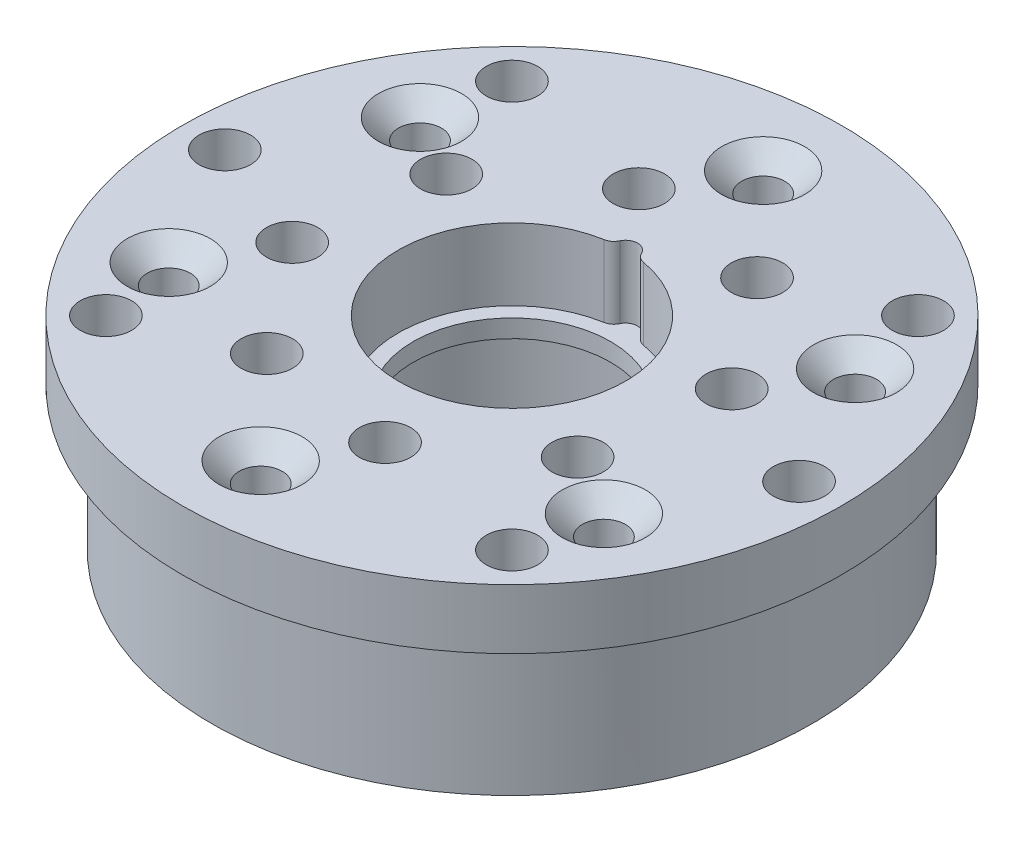
SolidWorks part; units mm, degrees
ref_plane "Front Plane" through (0, 0, 0) normal (0, 0, 1) x (1, 0, 0)
ref_plane "Top Plane" through (0, 0, 0) normal (0, 1, 0) x (1, 0, 0)
ref_plane "Right Plane" through (0, 0, 0) normal (1, 0, 0) x (0, 0, -1)
sketch "Sketch1" plane through (0, 0, 0) normal (0, 1, 0) x (1, 0, 0)
  circle A0 centre (0, 0) radius 21 construction
  circle A1 centre (0, 21) radius 2.5
  circle A2 centre (18.1865, 10.5) radius 2.5
  circle A3 centre (18.1865, -10.5) radius 2.5
  circle A4 centre (0, -21) radius 2.5
  circle A5 centre (-18.1865, -10.5) radius 2.5
  circle A6 centre (-18.1865, 10.5) radius 2.5
  circle A7 centre (0, 0) radius 25.1
  circle A8 centre (0, 0) radius 8.25
  point P18 (0, 0)
  dimension "D1" = 42
  dimension "D2" = 5
  dimension "D4" = 50.2
  dimension "D5" = 16.5
  dimension "D3" = 6
extrude "Boss-Extrude1" add sketch "Sketch1" along normal blind 10
sketch "Sketch2" plane through (0, 10, 0) normal (0, 1, 0) x (1, 0, 0)
  circle A0 centre (0, 0) radius 9.5
  circle A1 centre (0, 0) radius 15.5
  dimension "D1" = 19
  dimension "D2" = 6
extrude "Boss-Extrude2" add sketch "Sketch2" along normal blind 8.5
sketch "Sketch4" plane through (0, 10, 0) normal (0, 1, 0) x (1, 0, 0)
  circle A0 centre (0, 0) radius 9.5 construction
  circle A1 centre (0, 0) radius 8.25 construction
  circle A2 centre (0, 0) radius 9.5
  circle A3 centre (0, 0) radius 8.25
extrude "Boss-Extrude3" add sketch "Sketch4" along normal blind 2.5
sketch "Sketch3" plane through (0, 0, 0) normal (0, -1, 0) x (1, 0, 0)
  circle A0 centre (0, 0) radius 12.5
  dimension "D1" = 25
extrude "Cut-Extrude1" cut sketch "Sketch3" against normal blind 11
chamfer "Chamfer1" distance 3 angle 45 1 edges at (0, 11, -12.5)
sketch "Sketch5" plane through (0, 10, 0) normal (0, 1, 0) x (1, 0, 0)
  circle A0 centre (0, 21) radius 2.5
  circle A1 centre (18.1872, 10.4996) radius 2.5
  circle A2 centre (18.1872, -10.5011) radius 2.5
  circle A3 centre (0, -21.0014) radius 2.5
  circle A4 centre (-18.1872, -10.5011) radius 2.5
  circle A5 centre (-18.1872, 10.4996) radius 2.5
  circle A6 centre (0, 0) radius 25.1 construction
  circle A7 centre (0, 0) radius 25.1
  circle A8 centre (0, 0) radius 15.5 construction
  circle A9 centre (0, 0) radius 15.5
  circle A10 centre (0, 21) radius 2.5 construction
  point P15 (0, -0.0007)
  dimension "D2" = 6
extrude "Boss-Extrude4" add sketch "Sketch5" along normal blind 8.5
sketch "Sketch6" plane through (0, 18.5, 0) normal (0, 1, 0) x (1, 0, 0)
  circle A0 centre (0, 0) radius 25.1 construction
  circle A1 centre (0, 0) radius 25.1
  circle A2 centre (0, 0) radius 27.55
  dimension "D1" = 55.1
extrude "Boss-Extrude5" add sketch "Sketch6" against normal blind 5
sketch "Sketch8" plane through (0, 18.5, 0) normal (0, 1, 0) x (1, 0, 0)
  circle A0 centre (0, 9.5) radius 1
  circle A1 centre (0, 0) radius 9.5 construction
  circle A2 centre (0, 0) radius 9.5 construction
  dimension "D1" = 2
extrude "Cut-Extrude2" cut sketch "Sketch8" against normal up to surface (6 mm away) up to face at (0, 12.5, 9.5)
fillet "Fillet1" radius 1 2 edges at (0.9986, 15.5, -9.4474) (-0.9986, 15.5, -9.4474)
sketch "Sketch11" plane through (0, 18.5, 0) normal (0, 1, 0) x (1, 0, 0)
  line L0 (0, 0) -> (17.55, 30.3975) construction
  circle A0 centre (0, 0) radius 15 construction
  circle A1 centre (7.5, 12.9904) radius 2.15
  circle A2 centre (14.4889, 3.8823) radius 2.15
  circle A3 centre (12.9904, -7.5) radius 2.15
  circle A4 centre (3.8823, -14.4889) radius 2.15
  circle A5 centre (-7.5, -12.9904) radius 2.15
  circle A6 centre (-14.4889, -3.8823) radius 2.15
  circle A7 centre (0, 0) radius 24 construction
  circle A8 centre (-24, 0) radius 2.15
  circle A9 centre (-16.9706, 16.9706) radius 2.15
  circle A11 centre (16.9706, 16.9706) radius 2.15
  circle A12 centre (24, 0) radius 2.15
  circle A13 centre (16.9706, -16.9706) radius 2.15
  circle A14 centre (-12.9904, 7.5) radius 2.15
  circle A15 centre (-3.8823, 14.4889) radius 2.15
  circle A17 centre (-16.9706, -16.9706) radius 2.15
  circle A18 centre (0, -24) radius 2.15 [skipped]
  circle A19 centre (0, 24) radius 2.15 [skipped]
  point P18 (0, 0)
  point P32 (0, 0)
  point P35 (0, 0)
  point P40 (0, 0)
  point P41 (-5.5561, 21.5179)
  point P42 (0, 0)
  point P43 (0, 24)
  point P44 (0, 24)
  point P45 (0, 0)
  dimension "D2" = 30
  dimension "D3" = 4.3
  dimension "D5" = 48
  dimension "D6" = 8
  dimension "D1" = 60
  dimension "D4" = 8
extrude "Cut-Extrude3" cut sketch "Sketch11" against normal blind 4.8
sketch "Sketch12" plane through (0, 0, 0) normal (0, -1, 0) x (1, 0, 0)
  circle A0 centre (0, 0) radius 25.1 construction
  circle A1 centre (18.1865, 10.5) radius 2.5 construction
  circle A2 centre (18.1865, -10.5) radius 2.5 construction
  circle A3 centre (0, -21) radius 2.5 construction
  circle A4 centre (-18.1865, -10.5) radius 2.5 construction
  circle A5 centre (-18.1865, 10.5) radius 2.5 construction
  circle A6 centre (0, 21) radius 2.5 construction
  circle A7 centre (0, 0) radius 12.5 construction
  circle A8 centre (0, 0) radius 25.1
  circle A9 centre (18.1865, 10.5) radius 2.5
  circle A10 centre (18.1865, -10.5) radius 2.5
  circle A11 centre (0, -21) radius 2.5
  circle A12 centre (-18.1865, -10.5) radius 2.5
  circle A13 centre (-18.1865, 10.5) radius 2.5
  circle A14 centre (0, 21) radius 2.5
  circle A15 centre (0, 0) radius 12.5
extrude "Cut-Extrude4" cut sketch "Sketch12" against normal blind 1.5
sketch "Sketch14" plane through (0, 18.5, 0) normal (0, 1, 0) x (1, 0, 0)
  circle A0 centre (0, 21) radius 2.5 construction
  circle A1 centre (0, 21) radius 2.5
  circle A2 centre (0, 21) radius 1.5
  circle A3 centre (18.1872, 10.4996) radius 1.5
  circle A4 centre (18.1872, 10.4996) radius 2.5
  circle A5 centre (18.1872, -10.5011) radius 1.5
  circle A6 centre (18.1872, -10.5011) radius 2.5
  circle A7 centre (0, -21.0014) radius 1.5
  circle A8 centre (0, -21.0014) radius 2.5
  circle A9 centre (-18.1872, -10.5011) radius 1.5
  circle A10 centre (-18.1872, -10.5011) radius 2.5
  circle A11 centre (-18.1872, 10.4996) radius 1.5
  circle A12 centre (-18.1872, 10.4996) radius 2.5
  point P22 (0, -0.0007)
  dimension "D1" = 3
extrude "Boss-Extrude8" add sketch "Sketch14" against normal blind 4.5
hole_wizard "CSK for M3 socket countersunk head screw1" positions "Sketch15" profile "Sketch16" countersink size "M3" standard "DIN" end condition through all
sketch "Sketch15" plane through (0, 18.5, 0) normal (0, 1, 0) x (1, 0, 0)
  point P0 (0, 21)
  point P3 (18.1872, 10.4996)
  point P6 (18.1872, -10.5011)
  point P9 (0, -21.0014)
  point P12 (-18.1872, -10.5011)
  point P15 (-18.1872, 10.4996)
sketch "Sketch16" plane through (0, 18.5, -21) normal (1, 0, 0) x (0, 0, 1)
  line L0 (0, 0) -> (0, 17)
  line L1 (0, 17) -> (1.8, 17)
  line L2 (1.8, 17) -> (1.8, 1.67)
  line L3 (1.8, 1.67) -> (3.47, 0)
  line L5 (3.47, 0) -> (0, 0)
  line L6 (-1.8, 1.67) -> (-3.47, 0) construction
  line L11 (0, -6.35) -> (0, 107.95) construction
  dimension "Thru Hole Dia." = 3.6
  dimension "Thru Hole Depth" = 17
  dimension "Near C'Sink Dia." = 6.94
  dimension "Near C'Sink Angle" = 90
